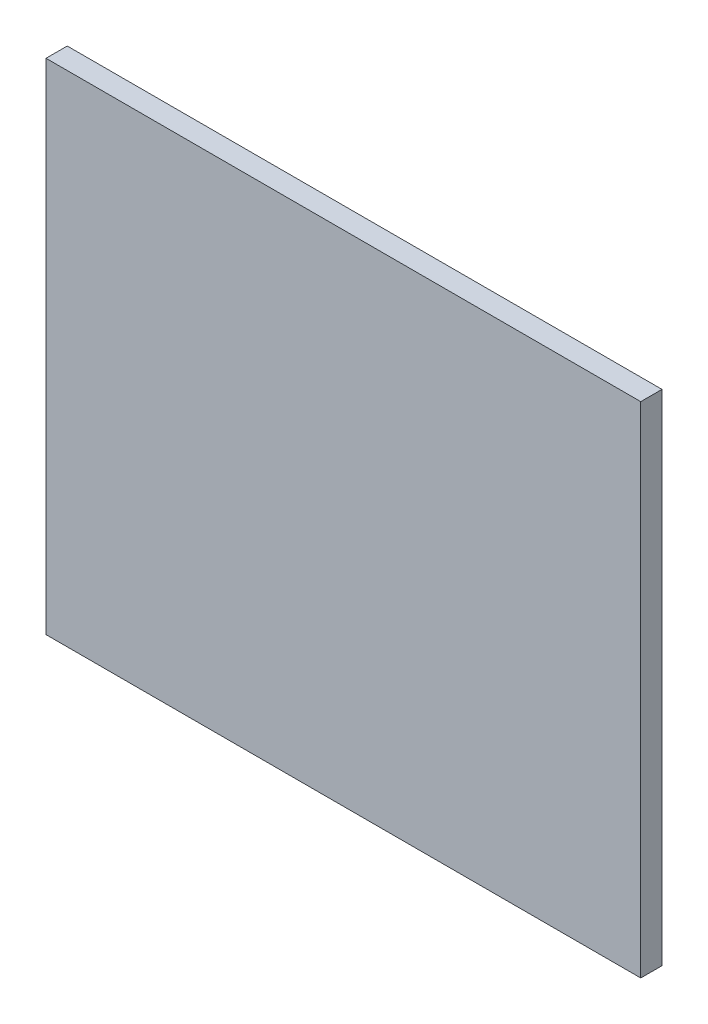
SolidWorks part; units mm, degrees
ref_plane "Front Plane" through (0, 0, 0) normal (0, 0, 1) x (1, 0, 0)
ref_plane "Top Plane" through (0, 0, 0) normal (0, 1, 0) x (1, 0, 0)
ref_plane "Right Plane" through (0, 0, 0) normal (1, 0, 0) x (0, 0, -1)
sketch "Sketch1" plane through (0, 0, 0) normal (0, 0, 1) x (1, 0, 0)
  line L1 (0, 0) -> (355.6, 0)
  line L2 (0, 0) -> (0, 298.45)
  line L3 (0, 298.45) -> (355.6, 298.45)
  line L4 (355.6, 0) -> (355.6, 298.45)
  dimension "D1" = 355.6
  dimension "D2" = 298.45
extrude "Boss-Extrude1" add sketch "Sketch1" along normal blind 12.7
